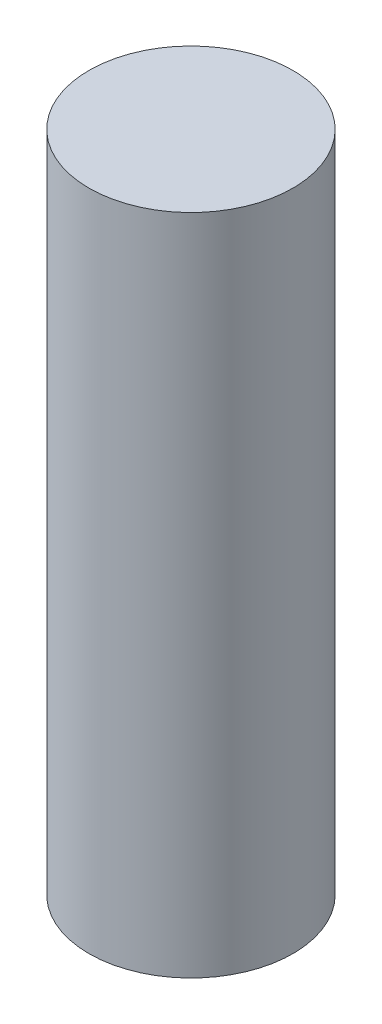
SolidWorks part; units mm, degrees
material "Silicon"
ref_plane "Front Plane" through (0, 0, 0) normal (0, 0, 1) x (1, 0, 0)
ref_plane "Top Plane" through (0, 0, 0) normal (0, 1, 0) x (1, 0, 0)
ref_plane "Right Plane" through (0, 0, 0) normal (1, 0, 0) x (0, 0, -1)
sketch "Main Parachute Bag Profile" plane through (0, 0, 0) normal (0, 1, 0) x (1, 0, 0)
  circle A0 centre (0, 0) radius 63.5
  dimension "D1" = 127
extrude "Main Parachute Bag Body" add sketch "Main Parachute Bag Profile" along normal blind 412.75 contours A0
equation "\"Packed Length\"=16.25"
equation "\"Packed Diameter\"= 5"
equation "\"D1@Main Parachute Bag Body\"=\"Packed Length\""
